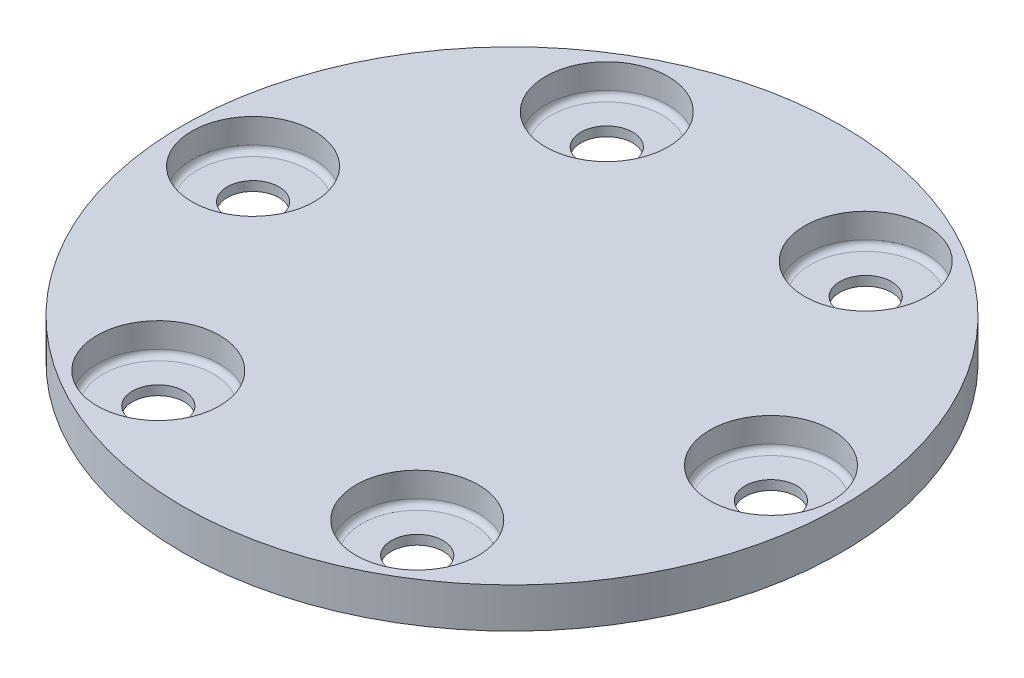
SolidWorks part; units mm, degrees
material "1060 Alloy"
ref_plane "Front Plane" through (0, 0, 0) normal (0, 0, 1) x (1, 0, 0)
ref_plane "Top Plane" through (0, 0, 0) normal (0, 1, 0) x (1, 0, 0)
ref_plane "Right Plane" through (0, 0, 0) normal (1, 0, 0) x (0, 0, -1)
sketch "Sketch1" plane through (0, 0, 0) normal (0, 1, 0) x (1, 0, 0)
  circle A0 centre (0, 0) radius 14
  dimension "D1" = 28
extrude "Boss-Extrude1" add sketch "Sketch1" along normal blind 1.7
sketch "Sketch7" plane through (0, 1.7, 0) normal (0, 1, 0) x (1, 0, 0)
  circle A0 centre (0, -10.25) radius 0.25
  circle A1 centre (0, 0) radius 9.8
  dimension "D1" = 0.5
  dimension "D2" = 10.25
  dimension "D3" = 19.6
sketch "Sketch8" plane through (0, 1.7, 0) normal (0, 1, 0) x (1, 0, 0)
  line L0 (0, 0) -> (13.2071, 13.2071) construction
  circle A0 centre (7.7782, 7.7782) radius 1
  dimension "D1" = 2
  dimension "D2" = 11
sketch "Sketch9" plane through (0, 1.7, 0) normal (0, 1, 0) x (1, 0, 0)
  circle A0 centre (0, 0) radius 11
  dimension "D1" = 22
hole_wizard "CBORE for M5 Hex Head Bolt1" positions "Sketch13" profile "Sketch14" counterbore size "M5" standard "ISO"
sketch "Sketch13" plane through (0, 1.7, 0) normal (0, 1, 0) x (1, 0, 0)
  circle A0 centre (0, 0) radius 11 construction
  point P0 (-11, 0)
  dimension "D1" = 11
sketch "Sketch14" plane through (-11, 1.7, 0) normal (1, 0, 0) x (0, 0, 1)
  line L0 (0, 0) -> (0, 5.6609)
  line L1 (0, 5.6609) -> (1.1, 5)
  line L2 (1.1, 5) -> (1.1, 1.3)
  line L3 (1.1, 1.3) -> (2.6, 1.3)
  line L4 (2.6, 1.3) -> (2.6, 0)
  line L5 (2.6, 0) -> (0, 0)
  line L10 (0, 5.6609) -> (-1.1, 5) construction
  line L11 (0, -6.35) -> (0, 107.95) construction
  dimension "Hole Dia." = 2.2
  dimension "Hole Depth" = 5
  dimension "C'Bore Dia." = 5.2
  dimension "C'Bore Depth" = 1.3
  dimension "Drill Angle" = 118
pattern_circular "CirPattern1" count 6 over 360 about axis through (0, 1.7, 0) along (0, 1, 0) of "CBORE for M5 Hex Head Bolt1"
fillet "Fillet1" radius 0.25 6 edges at (-11, 0.4, 2.6) (3.2483, 0.4, -10.8263) (-7.7517, 0.4, -8.2263) (-3.2483, 0.4, 10.8263) (7.7517, 0.4, 8.2263) (11, 0.4, -2.6)
